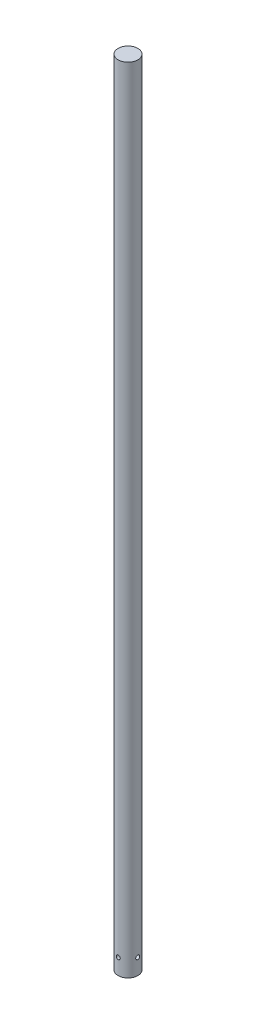
SolidWorks part; units mm, degrees
material "AISI 316 Annealed Stainless Steel Bar (SS)"
ref_plane "Front" through (0, 0, 0) normal (0, 0, 1) x (1, 0, 0)
ref_plane "Top" through (0, 0, 0) normal (0, 1, 0) x (1, 0, 0)
ref_plane "Right" through (0, 0, 0) normal (1, 0, 0) x (0, 0, -1)
sketch "Sketch1" plane through (0, 0, 0) normal (0, 1, 0) x (1, 0, 0)
  circle A1 centre (0, 0) radius 12.5
  dimension "D1" = 25
extrude "Boss-Extrude1" add sketch "Sketch1" along normal blind 1000
sketch "Sketch2" plane through (0, 1000, 0) normal (0, 1, 0) x (1, 0, 0)
  line L0 (-9.5, 8.124) -> (9.5, 8.124)
  arc A0 (9.5, 8.124) -> (-9.5, 8.124) centre (0, 0) ccw
  dimension "D1" = 25
  dimension "D2" = 19
extrude "Cut-Extrude1" [suppressed] cut sketch "Sketch2" against normal blind 300
sketch3d "3DSketch1"
  circle A0 centre (0, 970, 0) radius 12.5
  point P2 (0, 957.5, 0)
  dimension "D1" = 25
curve "Helix/Spiral1" pitch 800 height 200 turns 0.25
hole_wizard "#8 (0.199) Diameter Hole3" positions "3DSketch6" profile "Sketch11" hole size "#8" standard "ANSI Inch" end condition through all
sketch3d "3DSketch6"
  point P0 (-12.5, 20, 0)
  point P2 (0, 20, -12.5)
  dimension "D1" = 20
  dimension "D2" = 20
sketch "Sketch11" plane through (-12.5, 20, 0) normal (0, 1, 0) x (0, 0, 1)
  line L0 (0, 0) -> (0, 25)
  line L1 (0, 25) -> (2.5273, 25)
  line L2 (2.5273, 25) -> (2.5273, 0)
  line L5 (2.5273, 0) -> (0, 0)
  line L11 (0, -6.35) -> (0, 107.95) construction
  dimension "Thru Hole Dia." = 5.0546
  dimension "Thru Hole Depth" = 25
